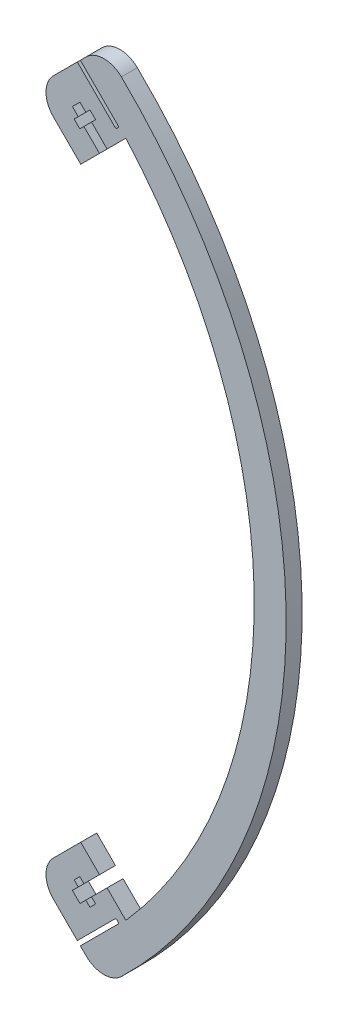
SolidWorks part; units mm, degrees
ref_plane "Front Plane" through (0, 0, 0) normal (0, 0, 1) x (1, 0, 0)
ref_plane "Top Plane" through (0, 0, 0) normal (0, 1, 0) x (1, 0, 0)
ref_plane "Right Plane" through (0, 0, 0) normal (1, 0, 0) x (0, 0, -1)
sketch "Sketch1" plane through (0, 0, 0) normal (0, 0, 1) x (1, 0, 0)
  line L0 (143.3604, 116.9193) -> (134.3442, 107.9031)
  line L1 (143.3604, -160.8213) -> (134.3442, -151.805)
  line L2 (143.3604, -160.8213) -> (128.1057, -145.5666) construction
  line L3 (128.1057, 101.6647) -> (143.3604, 116.9193) construction
  arc A0 (143.3604, 116.9193) -> (143.3604, -160.8213) centre (-21.951, -21.951) cw
  arc A1 (134.3442, 107.9031) -> (134.3442, -151.805) centre (-21.951, -21.951) cw
  arc A2 (143.3604, 116.9193) -> (131.0145, 130.4116) centre (-21.951, -21.951) ccw construction
  dimension "D1" = 12.7
extrude "Arc Extrusion" add sketch "Sketch1" along normal blind 6.35
ref_plane "Clothes Line Center Plane" through (0, -21.951, 0) normal (0, 1, 0) x (1, 0, 0)
sketch "Sketch4" plane through (0, 0, 6.35) normal (0, 0, 1) x (1, 0, 0)
  line L0 (134.3442, -151.805) -> (143.3604, -160.8213)
  line L1 (139.4438, -165.8849) -> (130.4636, -156.9046) construction
  line L2 (105.6551, -132.0962) -> (123.6156, -150.0567) construction
  line L3 (139.194, -165.6351) -> (112.2532, -138.6943)
  line L4 (112.2532, -138.6943) -> (94.2927, -156.6548)
  line L5 (94.2927, -156.6548) -> (121.204, -183.5661)
  arc A0 (143.3604, -160.8213) -> (139.194, -165.6351) centre (-21.951, -21.951) cw
  arc A1 (134.3442, -151.805) -> (130.1981, -156.6392) centre (-21.951, -21.951) cw
  arc A2 (139.194, -165.6351) -> (121.204, -183.5661) centre (-21.951, -21.951) cw
  arc A3 (134.3442, -151.805) -> (134.3442, 107.9031) centre (-21.951, -21.951) ccw construction
  arc A4 (143.3604, -160.8213) -> (143.3604, 116.9193) centre (-21.951, -21.951) ccw construction
  arc A5 (131.0145, -174.3136) -> (143.3604, -160.8213) centre (-21.951, -21.951) ccw construction
  line M8 (134.3442, -151.805) -> (143.3604, -160.8213)
  dimension "D1" = 25.4
  dimension "D2" = 38.1
extrude "Mount to V Funnel" add sketch "Sketch4" against normal up to surface (6.35 mm away) contours A1 L3 A0 M8 | A2 L3 L4 L5 region at (136.7864, -158.7357, 6.35) region at (116.8258, -161.2242, 6.35) up to face at (163.2257, -21.951, 0)
sketch "Sketch5" plane through (0, 0, 6.35) normal (0, 0, 1) x (1, 0, 0)
  line L0 (121.2256, -147.6667) -> (103.2651, -165.6272) construction
  line L1 (130.1981, -156.6392) -> (112.2532, -138.6943) construction
  line L2 (94.2927, -156.6548) -> (121.204, -183.5661) construction
  line L3 (130.1981, -156.6392) -> (112.2376, -174.5997)
  line L4 (112.2532, -138.6943) -> (94.2927, -156.6548) construction
  line B0 (122.7343, -149.1754) -> (119.717, -146.158)
  line B1 (111.2755, -154.5995) -> (109.6411, -152.9651)
  line B2 (109.6411, -152.9651) -> (111.8862, -150.72)
  line B3 (111.8862, -150.72) -> (113.5206, -152.3544)
  line B4 (113.5206, -152.3544) -> (119.717, -146.158)
  line B5 (111.2755, -154.5995) -> (108.9406, -156.9344)
  line B6 (108.9406, -156.9344) -> (111.958, -159.9517)
  line B7 (114.2929, -157.6169) -> (111.958, -159.9517)
  line B8 (116.5379, -155.3718) -> (122.7343, -149.1754)
  line B9 (118.1723, -157.0062) -> (116.5379, -155.3718)
  line B10 (115.9273, -159.2513) -> (118.1723, -157.0062)
  line B11 (114.2929, -157.6169) -> (115.9273, -159.2513)
  line M9 (130.1981, -156.6392) -> (112.2532, -138.6943)
sketch_block_instance "TSlot-1"
sketch_block "TSlot" parameters "D1"=3.302, "D2"=3.175
extrude "T Slot Hole" cut sketch "Sketch5" against normal through all contours L0 B6 B7 B11 B10 B9 B8 M9 | L0 B0 B4 B3 B2 B1 B5 B6 region at (116.5257, -154.4541, 6.35) region at (114.4382, -152.3667, 6.35)
mirror "Mount and T Slot Mirror" about plane through (0, -21.951, 0) normal (0, 1, 0) of "Mount to V Funnel", "T Slot Hole"
fillet "Mount Fillets" radius 10 4 edges at (94.2927, -156.6548, 3.175) (121.204, -183.5661, 3.175) (94.2927, 112.7529, 3.175) (121.204, 139.6642, 3.175)
sketch "Sketch6" plane through (0, 0, 6.35) normal (0, 0, 1) x (1, 0, 0)
  line L0 (110.8983, 129.3585) -> (126.2567, 114.0002)
  line L1 (101.3638, 119.8239) -> (114.3962, 132.8564) construction
  line L2 (126.2567, 114.0002) -> (127.4588, 115.2023)
  line L3 (127.4588, 115.2023) -> (112.1004, 130.5606)
  line L4 (115.9273, 115.3493) -> (118.1723, 113.1043) construction
  dimension "D1" = 1.7
  dimension "D2" = 21.72
  dimension "D3" = 6.35
extrude "Cut-Extrude1" cut sketch "Sketch6" against normal through all and the other way through all
mirror "Mirror1" about plane through (0, -21.951, 0) normal (0, 1, 0) of "Cut-Extrude1"
fillet "Fillet1" radius 0.5 4 edges at (127.4588, -159.1042, 3.175) (126.2567, -157.9021, 3.175) (126.2567, 114.0002, 3.175) (127.4588, 115.2023, 3.175)
